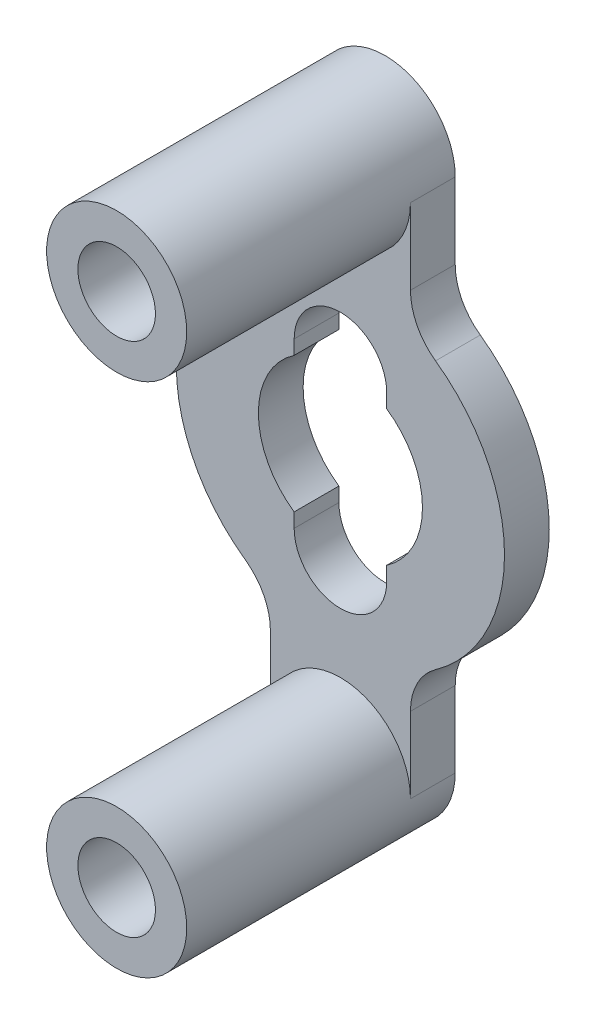
SolidWorks part; units mm, degrees
ref_plane "前视基准面" through (0, 0, 0) normal (0, 0, 1) x (1, 0, 0)
ref_plane "上视基准面" through (0, 0, 0) normal (0, 1, 0) x (1, 0, 0)
ref_plane "右视基准面" through (0, 0, 0) normal (1, 0, 0) x (0, 0, -1)
sketch "草图1" plane through (0, 0, 0) normal (0, 0, 1) x (1, 0, 0)
  line L0 (2.3479, 6.1111) -> (2.3479, 8.6521)
  line L7 (-1.55, -2.75) -> (-1.55, -2.2716)
  line L8 (1.55, -2.75) -> (1.55, -2.2716)
  line L9 (0, -8.6521) -> (0, -6.3042) construction
  line L10 (-2.3479, -8.6521) -> (-2.3479, -6.1111)
  line L11 (2.3479, -8.6521) -> (2.3479, -6.1111)
  line L13 (-1.55, 2.2716) -> (-1.55, 2.75)
  line L14 (-2.3479, 6.1111) -> (-2.3479, 8.6521)
  line L15 (0, 5.5) -> (0, 8.6521) construction
  line L17 (1.55, 2.2716) -> (1.55, 2.75)
  arc A0 (-3.1885, 4.4815) -> (-3.1885, -4.4815) centre (0, 0) ccw
  arc A1 (1.55, -2.2716) -> (1.55, 2.2716) centre (0, 0) ccw
  arc A2 (-1.55, -2.75) -> (1.55, -2.75) centre (0, -2.75) ccw
  arc A3 (1.55, 2.75) -> (-1.55, 2.75) centre (0, 2.75) ccw
  arc A4 (-2.3479, -8.6521) -> (2.3479, -8.6521) centre (0, -8.6521) ccw
  arc A5 (2.3479, 8.6521) -> (-2.3479, 8.6521) centre (0, 8.6521) ccw
  circle A6 centre (0, 8.6521) radius 2.3479
  circle A7 centre (0, -8.6521) radius 2.3479
  arc A8 (-1.55, 2.2716) -> (-1.55, -2.2716) centre (0, 0) ccw
  arc A9 (3.1885, -4.4815) -> (3.1885, 4.4815) centre (0, 0) ccw
  arc A10 (-2.3479, -6.1111) -> (-3.1885, -4.4815) centre (-4.3479, -6.1111) ccw
  arc A11 (2.3479, -6.1111) -> (3.1885, -4.4815) centre (4.3479, -6.1111) cw
  arc A12 (2.3479, 6.1111) -> (3.1885, 4.4815) centre (4.3479, 6.1111) ccw
  arc A13 (-2.3479, 6.1111) -> (-3.1885, 4.4815) centre (-4.3479, 6.1111) cw
  circle A14 centre (0, 8.6521) radius 1.3
  circle A15 centre (0, -8.6521) radius 1.3
  point P0 (0, 0)
  point P11 (0, 0)
  point P18 (0, 0)
  point P27 (2.3479, -4.9737)
  dimension "D3" = 5.5
  dimension "D4" = 1.55
  dimension "D1" = 2
extrude "凸台-拉伸1" add sketch "草图1" along normal blind 1.5 contours L14 A13 A0 A10 L10 A7 L11 A11 A9 A12 L0 A6 A8 L13 A3 L17 A1 L8 A2 L7 region at (2.3882, 5.1003, 0)
extrude "凸台-拉伸2" add sketch "草图1<4>" along normal blind 9 contours A4 A7 A15 | A5 A6 A14 region at (0, 6.3706, 0) region at (0, -10.9336, 0)
sketch "草图1<4>" plane through (0, 0, 0) normal (0, 0, 1) x (1, 0, 0) same geometry as "草图1"
